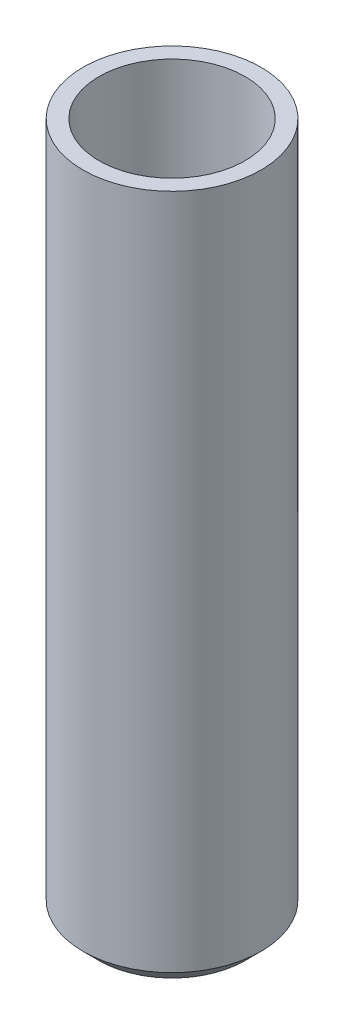
SolidWorks part; units mm, degrees
ref_plane "前视基准面" through (0, 0, 0) normal (0, 0, 1) x (1, 0, 0)
ref_plane "上视基准面" through (0, 0, 0) normal (0, 1, 0) x (1, 0, 0)
ref_plane "右视基准面" through (0, 0, 0) normal (1, 0, 0) x (0, 0, -1)
sketch "草图1" plane through (0, 0, 0) normal (0, 1, 0) x (1, 0, 0)
  circle A0 centre (0, 0) radius 2.5
  dimension "D1" = 5
extrude "凸台-拉伸1" add sketch "草图1" along normal blind 20
sketch "草图2" plane through (0, 0, 0) normal (0, -1, 0) x (1, 0, 0)
  circle A0 centre (0, 0) radius 2.05
  dimension "D1" = 4.1
extrude "切除-拉伸1" cut sketch "草图2" against normal through all
chamfer "倒角1" distance 1 angle 45 1 edges at (0, 0, 2.5)
